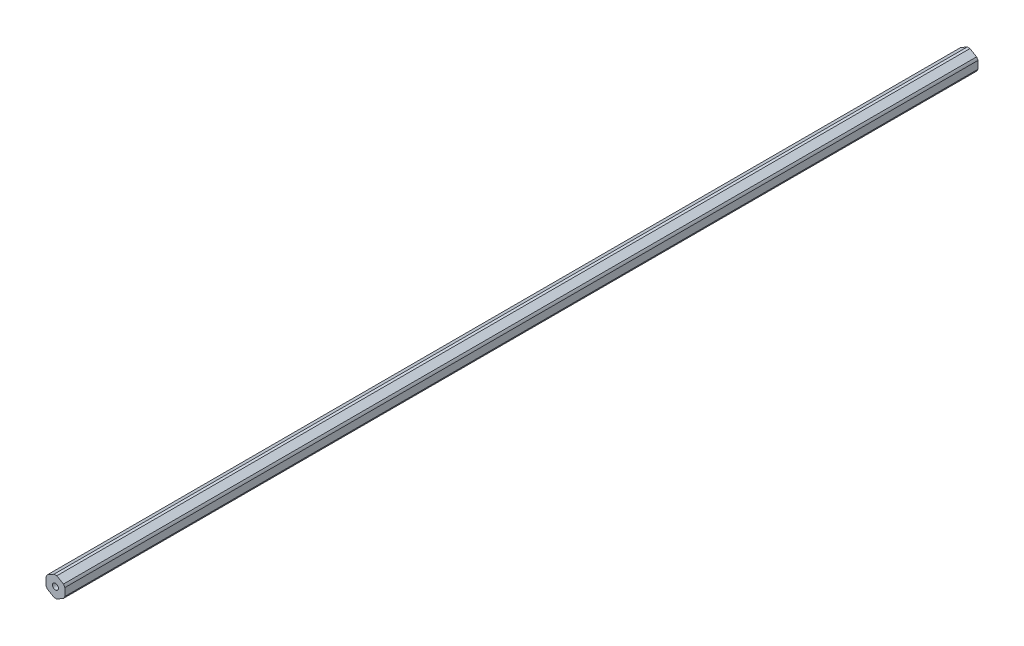
SolidWorks part; units mm, degrees
material "7075-T6 (SN)"
ref_plane "Front Plane" through (0, 0, 0) normal (0, 0, 1) x (1, 0, 0)
ref_plane "Top Plane" through (0, 0, 0) normal (0, 1, 0) x (1, 0, 0)
ref_plane "Right Plane" through (0, 0, 0) normal (1, 0, 0) x (0, 0, -1)
sketch "Sketch2" plane through (0, 0, 0) normal (0, 0, 1) x (1, 0, 0)
  line L1 (0, 7.3323) -> (-6.35, 3.6662)
  line L2 (-6.35, 3.6662) -> (-6.35, -3.6662)
  line L3 (-6.35, -3.6662) -> (0, -7.3323)
  line L4 (0, -7.3323) -> (6.35, -3.6662)
  line L5 (6.35, -3.6662) -> (6.35, 3.6662)
  line L6 (6.35, 3.6662) -> (0, 7.3323)
  circle A0 centre (0, 0) radius 6.35 construction
  circle A2 centre (0, 0) radius 2.0193
  circle A3 centre (0, 0) radius 6.858
  dimension "D1" = 12.7
  dimension "D2" = 13.716
  dimension "D3" = 4.0386
extrude "Boss-Extrude1" add sketch "Sketch2" along normal mid plane 615.95 contours L5 A3 L6 L1 L2 L3 L4 A2 region at (0, 6.6711, 0)
hole_wizard "#10-32 Tapped Hole2" positions "3DSketch1" profile "Sketch6" tap size "#10-32" standard "ANSI Inch"
sketch3d "3DSketch1"
  circle A0 centre (0, 0, 307.975) radius 2.0193 construction
  circle A1 centre (0, 0, -307.975) radius 2.0193 construction
  point P0 (0, 0, -307.975)
  point P2 (0, 0, 307.975)
  point P7 (0, 0, 309.9943)
  point P10 (0, 0, -305.9557)
sketch "Sketch6" plane through (0, 0, -307.975) normal (1, 0, 0) x (0, 1, 0)
  line L0 (0, 0) -> (0, 17.5608)
  line L1 (0, 17.5608) -> (2.0193, 16.3474)
  line L2 (2.0193, 16.3474) -> (2.0193, 0)
  line L5 (2.0193, 0) -> (0, 0)
  line L10 (0, 17.5608) -> (-2.0193, 16.3474) construction
  line L11 (0, -6.35) -> (0, 107.95) construction
  dimension "Tap Drill Dia." = 4.0386
  dimension "Tap Drill Depth" = 16.3474
  dimension "Drill Angle" = 118
cosmetic thread "Hole Thread2" parameters "D1"=13.97, "D2"=4.826
cosmetic thread "Hole Thread3" parameters "D1"=13.97, "D2"=4.826
